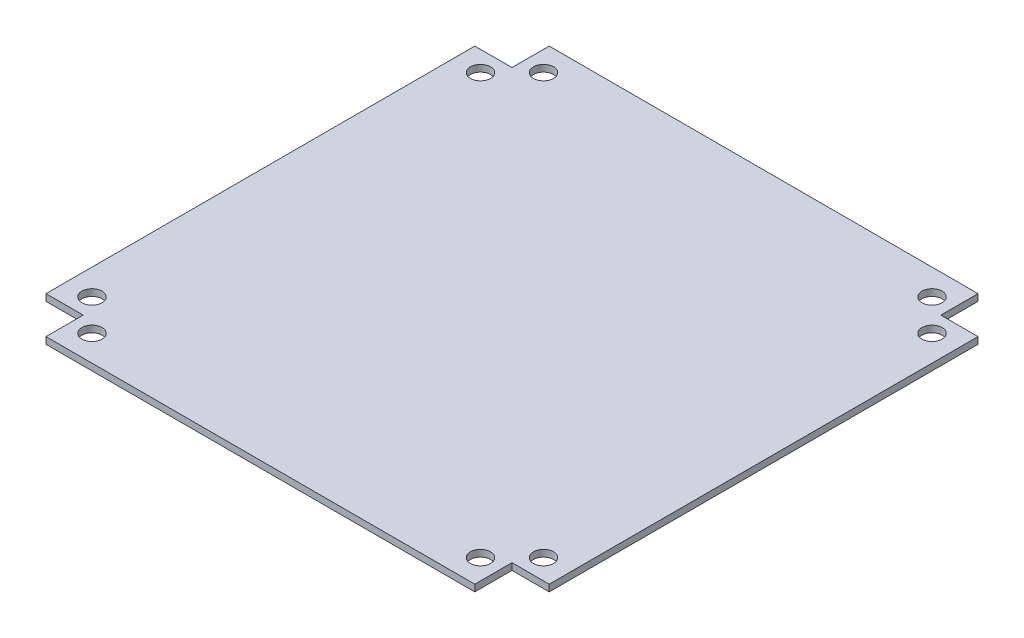
SolidWorks part; units mm, degrees
ref_plane "Front Plane" through (0, 0, 0) normal (0, 0, 1) x (1, 0, 0)
ref_plane "Top Plane" through (0, 0, 0) normal (0, 1, 0) x (1, 0, 0)
ref_plane "Right Plane" through (0, 0, 0) normal (1, 0, 0) x (0, 0, -1)
sketch "Sketch1" plane through (0, 0, 0) normal (0, 1, 0) x (1, 0, 0)
  line L1 (0, 0) -> (97.4, 0)
  line L2 (0, 0) -> (0, 97.4)
  line L3 (0, 97.4) -> (97.4, 97.4)
  line L4 (97.4, 0) -> (97.4, 97.4)
  line L5 (0, 0) -> (7.2, 0)
  line L6 (0, 0) -> (0, 7.2)
  line L7 (0, 7.2) -> (7.2, 7.2)
  line L8 (7.2, 0) -> (7.2, 7.2)
  line L9 (0, 97.4) -> (7.2, 97.4)
  line L10 (0, 97.4) -> (0, 90.2)
  line L11 (0, 90.2) -> (7.2, 90.2)
  line L12 (7.2, 97.4) -> (7.2, 90.2)
  line L13 (97.4, 97.4) -> (90.2, 97.4)
  line L14 (97.4, 97.4) -> (97.4, 90.2)
  line L15 (97.4, 90.2) -> (90.2, 90.2)
  line L16 (90.2, 97.4) -> (90.2, 90.2)
  line L17 (97.4, 0) -> (90.2, 0)
  line L18 (97.4, 0) -> (97.4, 7.2)
  line L19 (97.4, 7.2) -> (90.2, 7.2)
  line L20 (90.2, 0) -> (90.2, 7.2)
  dimension "D1" = 7.2
  dimension "D2" = 7.2
  dimension "D3" = 7.2
  dimension "D4" = 7.2
  dimension "D5" = 97.4
  dimension "D6" = 7.2
  dimension "D7" = 7.2
  dimension "D8" = 97.4
  dimension "D9" = 7.2
  dimension "D10" = 7.2
extrude "Boss-Extrude1" add sketch "Sketch1" along normal blind 1.3 contours L1 L20 L19 L4 L15 L16 L3 L12 L11 L2 L7 L8 region at (48.7, 0, -48.7)
sketch "Sketch2" plane through (0, 0, 0) normal (0, -1, 0) x (1, 0, 0)
  line L0 (7.2, 0) -> (90.2, 0) construction
  line L1 (97.4, -7.2) -> (97.4, -90.2) construction
  line L2 (0, -7.2) -> (0, -90.2) construction
  line L3 (0, -90.2) -> (7.2, -90.2) construction
  line L4 (7.2, -97.4) -> (90.2, -97.4) construction
  line L5 (7.2, -97.4) -> (7.2, -90.2) construction
  line L6 (0, -7.2) -> (7.2, -7.2) construction
  line L7 (90.2, -97.4) -> (90.2, -90.2) construction
  line L8 (97.4, -90.2) -> (90.2, -90.2) construction
  line L9 (7.2, 0) -> (7.2, -7.2) construction
  line L10 (90.2, 0) -> (90.2, -7.2) construction
  line L11 (97.4, -7.2) -> (90.2, -7.2) construction
  circle A0 centre (92.4, -86.3) radius 1.95
  circle A1 centre (86.3, -92.4) radius 1.95
  circle A2 centre (11.1, -92.4) radius 1.95
  circle A3 centre (5, -86.3) radius 1.95
  circle A4 centre (5, -11.1) radius 1.95
  circle A5 centre (11.1, -5) radius 1.95
  circle A6 centre (86.3, -5) radius 1.95
  circle A7 centre (92.4, -11.1) radius 1.95
  point P26 (9.3106, -97.4)
  point P27 (41.8272, -109.2025)
  point P28 (85.2805, -97.4)
  dimension "D1" = 3.9
  dimension "D2" = 3.9
  dimension "D3" = 3.9
  dimension "D4" = 3.9
  dimension "D5" = 3.9
  dimension "D6" = 3.9
  dimension "D7" = 3.9
  dimension "D8" = 3.9
  dimension "D9" = 3.9
  dimension "D10" = 3.9
  dimension "D11" = 3.9
  dimension "D12" = 3.9
  dimension "D13" = 5
  dimension "D14" = 5
  dimension "D15" = 5
  dimension "D16" = 5
  dimension "D17" = 5
  dimension "D18" = 5
  dimension "D19" = 3.9
  dimension "D20" = 3.9
  dimension "D21" = 3.9
  dimension "D22" = 5
  dimension "D23" = 5
  dimension "D24" = 3.9
extrude "Cut-Extrude1" cut sketch "Sketch2" against normal blind 1.3
